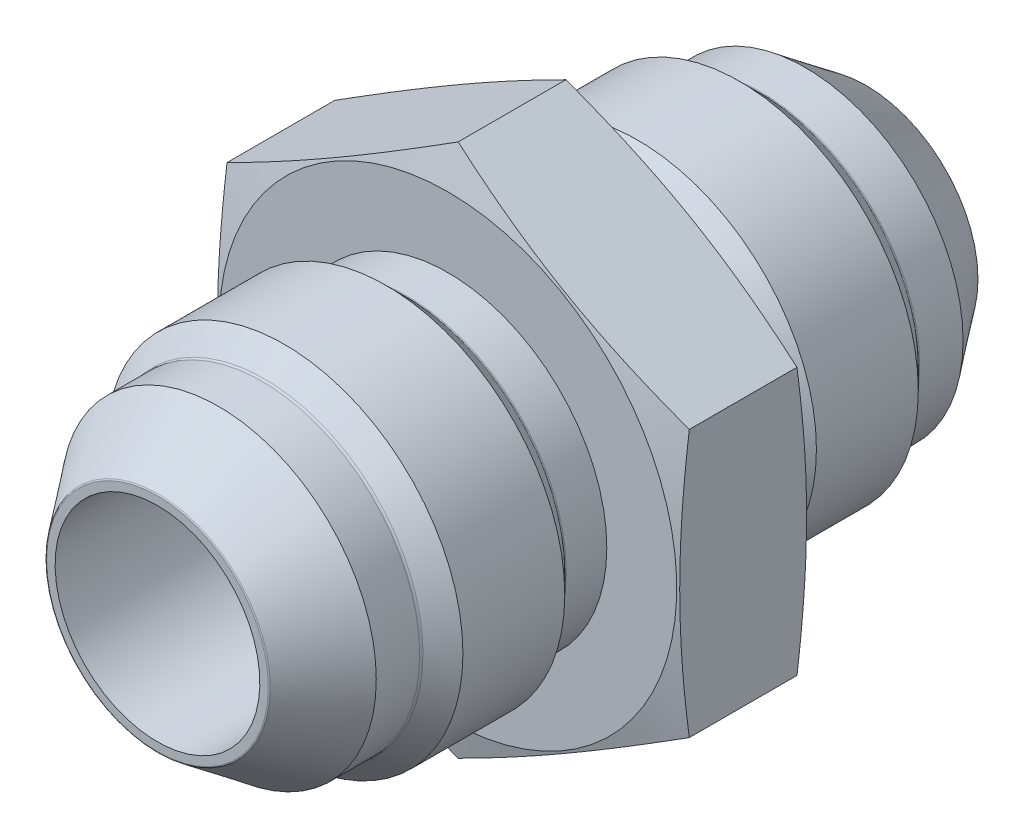
SolidWorks part; units mm, degrees
material "2024-T4"
ref_plane "Front Plane" through (0, 0, 0) normal (0, 0, 1) x (1, 0, 0)
ref_plane "Top Plane" through (0, 0, 0) normal (0, 1, 0) x (1, 0, 0)
ref_plane "Right Plane" through (0, 0, 0) normal (1, 0, 0) x (0, 0, -1)
sketch "Sketch0" plane through (0, 0, 0) normal (1, 0, 0) x (0, 0, -1)
  line L0 (-26.7843, 0) -> (0, 0) construction
  line L1 (0, 0) -> (26.7843, 0) construction
  line L2 (-18.7833, 13.4937) -> (-18.7833, -13.4937) construction
  line L3 (-26.7843, 7.7343) -> (-26.7843, -7.7343) construction
  line L4 (-26.7843, 8.4328) -> (-26.7843, -8.4328) construction
  line L5 (-22.1664, 11.9126) -> (-22.1664, -11.9126) construction
  line L6 (-26.7843, 8.4328) -> (-22.1664, 11.9126) construction
  line L7 (-22.1664, 11.9126) -> (-18.7833, 11.9126) construction
  line L8 (-18.7833, 11.9126) -> (-18.7833, -11.9126) construction
  line L9 (-4.8387, 17.4625) -> (-4.8387, -17.4625) construction
  line L10 (-4.8387, 17.2847) -> (-4.8387, -17.2847) construction
  line L11 (-18.7833, 11.9126) -> (-18.7833, 13.4937) construction
  line L12 (-18.7833, 13.4937) -> (-8.0137, 13.4937) construction
  line L13 (-8.0137, 13.4937) -> (-8.0137, 12.0015) construction
  line L14 (-8.0137, 12.0015) -> (-4.8387, 12.0015) construction
  line L15 (-8.0137, 12.0015) -> (-8.0137, -12.0015) construction
  line L16 (-4.8387, 0) -> (-5.0419, 0) construction
  point P8 (-4.8387, 0)
  point P13 (-22.1664, 0)
  point P14 (-18.7833, 0)
  point P24 (-8.0137, 0)
  point P26 (-4.8387, 0)
  point P27 (4.8387, 0)
  dimension "37" = 37
sketch "Sketch1" plane through (0, 0, 0) normal (1, 0, 0) x (0, 0, -1)
  line L0 (-26.7843, 0) -> (0, 0)
  line L1 (-26.7843, 0) -> (-26.7843, 8.3695)
  line L2 (-26.7337, 8.4709) -> (-22.1664, 11.9126)
  line L3 (-22.1664, 11.9126) -> (-18.8885, 11.9126)
  line L4 (-18.7089, 11.987) -> (-17.2021, 13.4937)
  line L5 (-17.2021, 13.4937) -> (-9.506, 13.4937)
  line L6 (-9.506, 13.4937) -> (-8.0881, 12.0759)
  line L7 (-7.9085, 12.0015) -> (0, 12.0015)
  line L8 (0, 12.0015) -> (0, 0)
  line L10 (-18.7833, 13.4937) -> (-18.7833, -13.4937) construction
  line L11 (-19.812, 0) -> (0, 0) construction
  line L12 (-26.7843, 7.7343) -> (-26.7843, -7.7343) construction
  line L13 (-18.7833, 13.4937) -> (-8.0137, 13.4937) construction
  line L15 (-8.0137, 13.4937) -> (-8.0137, 12.0015) construction
  arc A0 (-26.7843, 8.3695) -> (-26.7337, 8.4709) centre (-26.6573, 8.3695) cw
  arc A1 (-18.8885, 11.9126) -> (-18.7089, 11.987) centre (-18.8885, 12.1666) ccw
  arc A2 (-8.0881, 12.0759) -> (-7.9085, 12.0015) centre (-7.9085, 12.2555) ccw
  point P27 (-26.7843, 8.4328)
  point P30 (-18.7833, 11.9126)
  point P33 (-8.0137, 12.0015)
  dimension "D1" = 0.127
  dimension "D2" = 0.254
  dimension "D3" = 45
  dimension "D4" = 45
revolve "Revolve1" add sketch "Sketch1" angle 360 about L11
sketch "Sketch2" plane through (0, 0, 26.7843) normal (0, 0, 1) x (1, 0, 0)
  circle A0 centre (0, 0) radius 13.4938
  point P3 (0, 13.4937)
curve "Helix/Spiral1" [suppressed] pitch 2.1167 height 24.0623 turns 11.368 parameters "Pitch"=2.1167
sketch "Sketch3" plane through (0, 0, 0) normal (1, 0, 0) x (0, 0, -1)
  line L0 (-28.7687, 13.7229) -> (-27.7103, 11.8898) construction
  line L1 (-27.7103, 11.8898) -> (-26.652, 13.7229) construction
  line L2 (-26.652, 13.7229) -> (-28.7687, 13.7229) construction
  line L3 (-26.7843, 13.4937) -> (-28.6364, 13.4937) construction
  line L4 (-27.7103, 13.7229) -> (-27.7103, 13.4937) construction
  line L5 (-27.9308, 12.2717) -> (-27.4899, 12.2717) construction
  line L6 (-27.7103, 12.2717) -> (-27.7103, 11.8898) construction
  line L7 (-28.7025, 13.6083) -> (-28.0411, 12.4626)
  line L8 (-28.7025, 13.6083) -> (-26.7182, 13.6083)
  line L9 (-26.7182, 13.6083) -> (-27.3796, 12.4626)
  line L10 (-27.7103, 11.8898) -> (-27.7103, -13.4937) construction
  line L11 (-27.7103, -13.4937) -> (-25.5937, -13.4937) construction
  line L12 (-25.5937, -13.4937) -> (-23.477, -13.4937) construction
  line L13 (-23.477, -13.4937) -> (-21.3603, -13.4937) construction
  line L14 (-21.3603, -13.4937) -> (-19.2437, -13.4938) construction
  line L15 (-19.2437, -13.4938) -> (-17.127, -13.4937) construction
  line L16 (-17.127, -13.4937) -> (-15.0103, -13.4938) construction
  line L17 (-15.0103, -13.4938) -> (-12.8937, -13.4937) construction
  line L21 (-17.2021, -13.4937) -> (-9.506, -13.4937) construction
  arc A0 (-28.0411, 12.4626) -> (-27.3796, 12.4626) centre (-27.7103, 12.6536) ccw
  point P13 (-27.7103, 13.6083)
sweep "Cut-Sweep1" [suppressed] cut profiles "Sketch3" path "Helix/Spiral1"
ref_axis "Axis1" through (-10.4775, 0, 0) along (1, 0, 0)
pattern_circular "CirPattern1" count 2 over 180 about axis through (-10.4775, 0, 0) along (1, 0, 0) reverse direction yes of bodies 102 103
sketch "Sketch4" plane through (0, 0, 0) normal (0, 0, 1) x (1, 0, 0)
  line L1 (0, 20.164) -> (-17.4625, 10.082)
  line L2 (-17.4625, 10.082) -> (-17.4625, -10.082)
  line L3 (-17.4625, -10.082) -> (0, -20.164)
  line L4 (0, -20.164) -> (17.4625, -10.082)
  line L5 (17.4625, -10.082) -> (17.4625, 10.082)
  line L6 (17.4625, 10.082) -> (0, 20.164)
  circle A0 centre (0, 0) radius 17.4625 construction
extrude "Boss-Extrude1" add sketch "Sketch4" along normal up to vertex (4.8387 mm away) and the other way up to vertex (4.8387 mm away) up to point (0, 0, 4.8387) other way up to point (0, 0, -4.8387)
sketch "Sketch5" plane through (0, 0, 0) normal (1, 0, 0) x (0, 0, -1)
  line L0 (-4.8387, 23.0432) -> (4.8387, 23.0432)
  line L1 (-4.8387, 23.0432) -> (-4.8387, 17.2847)
  line L2 (-4.8387, 17.2847) -> (-4.0672, 20.164)
  line L3 (-4.0672, 20.164) -> (4.0672, 20.164)
  line L4 (4.0672, 20.164) -> (4.8387, 17.2847)
  line L5 (4.8387, 17.2847) -> (4.8387, 23.0432)
  line L7 (-4.8387, 20.164) -> (4.8387, 20.164) construction
  line L8 (-4.8387, 0) -> (0, 0) construction
  dimension "D1" = 15
revolve "Cut-Revolve1" cut sketch "Sketch5" angle 360 about L8
sketch "Sketch6" plane through (0, 0, 0) normal (1, 0, 0) x (0, 0, -1)
  line L0 (-26.7843, 7.7343) -> (0, 7.7343)
  line L1 (7.7343, 0) -> (-26.7843, 0)
  line L2 (-26.7843, 0) -> (-26.7843, 7.7343)
  arc A0 (0, 7.7343) -> (7.7343, 0) centre (0, 0) cw
revolve "Cut-Revolve2" cut sketch "Sketch6" angle 360 about L1
pattern_circular "CirPattern2" count 2 every 180 about axis through (-10.4775, 0, 0) along (1, 0, 0) of "Cut-Revolve2" reverse direction yes
equation "\"D3@Helix/Spiral1\" = \"Pitch@Helix/Spiral1\" + \"J@Sketch0\""
equation "\"P@Sketch3\" = \"Pitch@Helix/Spiral1\""
equation "\"H/8@Sketch3\" = \"H@Sketch3\" / 8"
equation "\"2/3H@Sketch3\" = 2/3 * \"H@Sketch3\""
